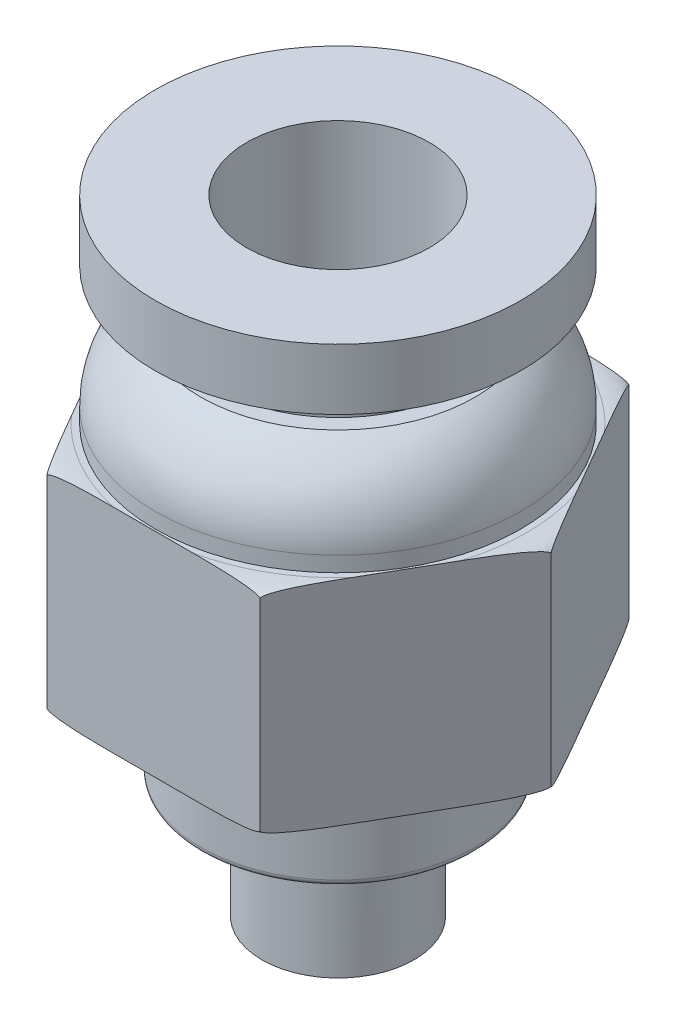
SolidWorks part; units mm, degrees
ref_plane "前视基准面" through (0, 0, 0) normal (0, 0, 1) x (1, 0, 0)
ref_plane "上视基准面" through (0, 0, 0) normal (0, 1, 0) x (1, 0, 0)
ref_plane "右视基准面" through (0, 0, 0) normal (1, 0, 0) x (0, 0, -1)
sketch "草图1" plane through (0, 0, 0) normal (0, 0, 1) x (1, 0, 0)
  line L0 (0, 26.7594) -> (0, -26.7594) construction
  line L1 (3, 20.5) -> (6, 20.5)
  line L2 (6, 20.5) -> (6, 18.5)
  line L3 (6, 18.5) -> (3.5, 18.5)
  line L4 (3.5, 18.5) -> (3.5, 17.5)
  line L5 (3.5, 17.5) -> (4, 17.5)
  line L6 (4, 17.5) -> (4, 17)
  line L7 (4, 17) -> (4.5, 17)
  line L8 (3, 20.5) -> (3, 8.5)
  line L9 (6, 14.5) -> (6, 14)
  line L10 (6, 14) -> (7, 14)
  line L11 (7, 14) -> (7, 7)
  line L12 (7, 7) -> (2.5, 7)
  line L13 (2.5, 7) -> (2.5, 0)
  line L14 (2.5, 0) -> (0, 0)
  line L15 (0, 0) -> (0, 8.5)
  line L16 (3, 8.5) -> (0, 8.5)
  line L17 (0, 8.5) -> (0, 0)
  line L18 (0, 0) -> (-0.0662, -0.1188)
  arc A0 (4.5, 17) -> (6, 14.5) centre (3.1667, 14.5) cw
  point P4 (0, 0)
  dimension "D1" = 12
  dimension "D2" = 2
  dimension "D3" = 12
  dimension "D4" = 0.5
  dimension "D5" = 0.5
  dimension "1." = 2
  dimension "D7" = 1
  dimension "D8" = 0.5
  dimension "D9" = 4.5
  dimension "D10" = 14
  dimension "D11" = 0.5
  dimension "D12" = 7
  dimension "D13" = 7
  dimension "D14" = 5
  dimension "D15" = 6
  dimension "D19" = 12
revolve "旋转1" add sketch "草图1" angle 360 about L0 region at (3.5964, 9.959, 0)
chamfer "倒角1" [suppressed] distance 0.5 angle 30
fillet "圆角1" radius 0.8 2 edges at (0, 7, 7) (0, 14, 7) second distance 0.2 first distance on face at (0, 7, 2.5) first distance on face at (0, 14, 7)
sketch "草图2" plane through (0, 0, 0) normal (0, 1, 0) x (1, 0, 0)
  line L1 (2, 1.1547) -> (0, 2.3094)
  line L2 (0, 2.3094) -> (-2, 1.1547)
  line L3 (-2, 1.1547) -> (-2, -1.1547)
  line L4 (-2, -1.1547) -> (0, -2.3094)
  line L5 (0, -2.3094) -> (2, -1.1547)
  line L6 (2, -1.1547) -> (2, 1.1547)
  circle A0 centre (0, 0) radius 2 construction
  dimension "D1" = 4
extrude "切除-拉伸1" [suppressed] cut sketch "草图2" along normal up to surface (8.5 mm away) up to face at (0, 8.5, 3)
sketch "草图3" plane through (0, 0, 0) normal (0, 1, 0) x (1, 0, 0)
  line L1 (7, 0) -> (3.5, 6.0622)
  line L2 (3.5, 6.0622) -> (-3.5, 6.0622)
  line L3 (-3.5, 6.0622) -> (-7, 0)
  line L4 (-7, 0) -> (-3.5, -6.0622)
  line L5 (-3.5, -6.0622) -> (3.5, -6.0622)
  line L6 (3.5, -6.0622) -> (7, 0)
  circle A0 centre (0, 0) radius 6.0622 construction
  circle A1 centre (0, 0) radius 7 construction
  circle A2 centre (0, 0) radius 12
  dimension "D1" = 5
extrude "切除-拉伸3" cut sketch "草图3" along normal through all
sketch "草图4" plane through (0, 7, 0) normal (0, -1, 0) x (1, 0, 0)
  circle A0 centre (0, 0) radius 2.5 construction
  circle A1 centre (0, 0) radius 2.5
  circle A2 centre (0, 0) radius 4.5
  dimension "D1" = 9
extrude "凸台-拉伸1" add sketch "草图4" along normal blind 3
sketch "草图5" plane through (0, 0, 0) normal (0, -1, 0) x (1, 0, 0)
  circle A0 centre (0, 0) radius 1
  dimension "D1" = 2
extrude "切除-拉伸4" cut sketch "草图5" against normal up to surface (8.5 mm away) up to face at (0, 8.5, 3)
fillet "圆角2" radius 0.2 1 edges at (0, 4, -4.5)
